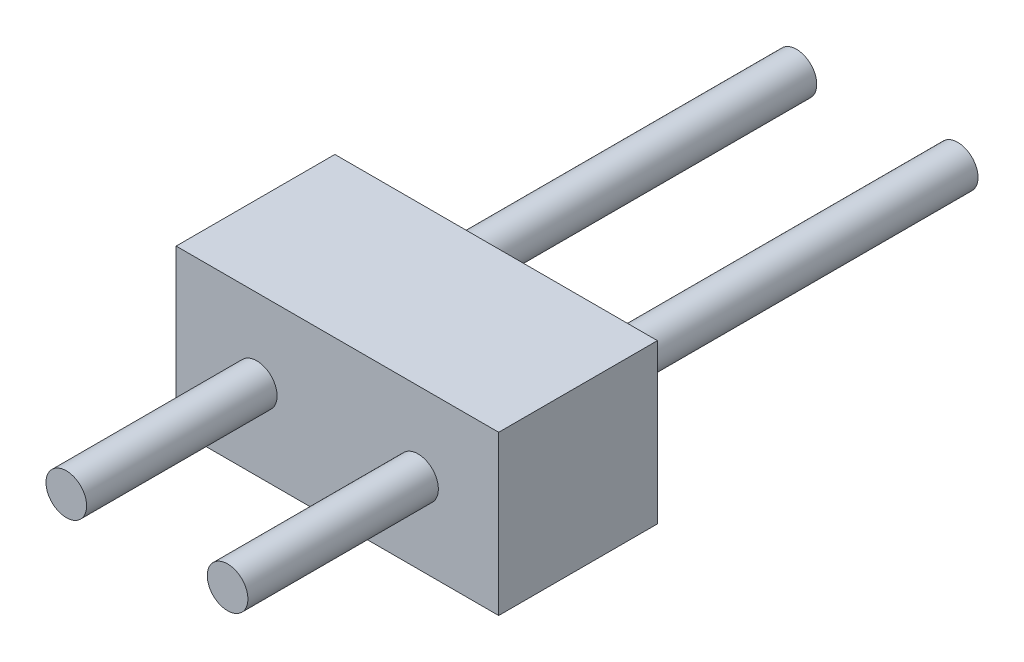
SolidWorks part; units mm, degrees
ref_plane "前视基准面" through (0, 0, 0) normal (0, 0, 1) x (1, 0, 0)
ref_plane "上视基准面" through (0, 0, 0) normal (0, 1, 0) x (1, 0, 0)
ref_plane "右视基准面" through (0, 0, 0) normal (1, 0, 0) x (0, 0, -1)
sketch "Sketch1" plane through (0, 0, 0) normal (0, 0, 1) x (1, 0, 0)
  line L1 (0, 0) -> (5.08, 0)
  line L2 (0, 0) -> (0, 2.5)
  line L3 (0, 2.5) -> (5.08, 2.5)
  line L4 (5.08, 0) -> (5.08, 2.5)
extrude "Boss-Extrude1" add sketch "Sketch1" along normal blind 2.5
sketch "Sketch2" plane through (0, 0, 2.5) normal (0, 0, 1) x (1, 0, 0)
  line L0 (5.08, 2.5) -> (0, 2.5) construction
  line L1 (2.54, 2.5) -> (2.54, -0.9621) construction
  circle A0 centre (1.27, 1.25) radius 0.32
  circle A1 centre (3.81, 1.25) radius 0.32
  dimension "D1" = 0.64
  dimension "D2" = 1.25
  dimension "D3" = 1.27
extrude "Boss-Extrude2" add sketch "Sketch2" along normal blind 3
extrude "Boss-Extrude3" add sketch "Sketch2<2>" against normal blind 6 from surface starting at face at (2.54, 1.25, 0)
sketch "Sketch2<2>" plane through (0, 0, 2.5) normal (0, 0, 1) x (1, 0, 0) same geometry as "Sketch2"
